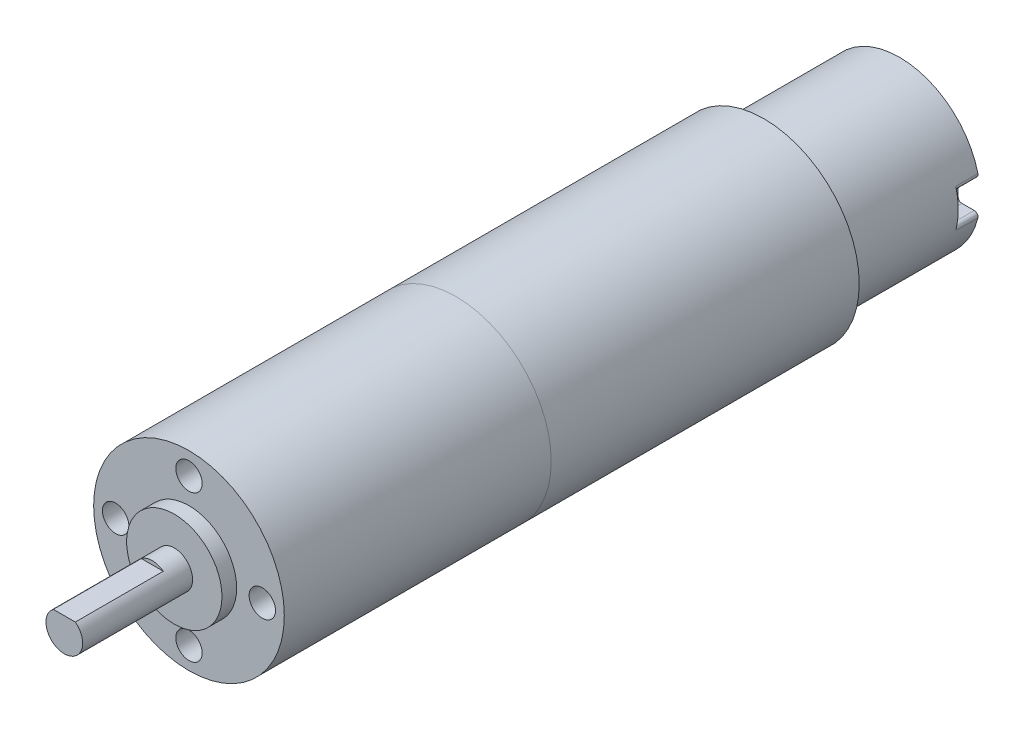
SolidWorks part; units mm, degrees
ref_plane "Plan de face" through (0, 0, 0) normal (0, 0, 1) x (1, 0, 0)
ref_plane "Plan de dessus" through (0, 0, 0) normal (0, 1, 0) x (1, 0, 0)
ref_plane "Plan de droite" through (0, 0, 0) normal (1, 0, 0) x (0, 0, -1)
sketch "Esquisse1" plane through (0, 0, 0) normal (0, 0, 1) x (1, 0, 0)
  circle A0 centre (0, 0) radius 13
  dimension "D1" = 26
extrude "Boss.-Extru. Reducteur" add sketch "Esquisse1" along normal blind 36.4
sketch "Esquisse2" plane through (0, 0, 36.4) normal (0, 0, 1) x (1, 0, 0)
  circle A0 centre (0, 0) radius 2.5
  dimension "D1" = 5
extrude "Boss.-Extru. Arbre" add sketch "Esquisse2" along normal blind 17
sketch "Esquisse4" plane through (0, 0, 36.4) normal (0, 0, 1) x (1, 0, 0)
  circle A0 centre (0, 0) radius 6.5
  circle A1 centre (0, 0) radius 2.5
extrude "Boss.-Extru.3" add sketch "Esquisse4" along normal blind 2
sketch "Esquisse5" plane through (0, 0, 36.4) normal (0, 0, 1) x (1, 0, 0)
  line L0 (0, 0) -> (10, 0) construction
  line L1 (0, 0) -> (0, 10) construction
  line L2 (0, 0) -> (-10, 0) construction
  line L3 (0, 0) -> (0, -10) construction
  circle A0 centre (0, 10) radius 1.8
  circle A1 centre (-10, 0) radius 1.8
  circle A2 centre (0, -10) radius 1.8
  circle A3 centre (10, 0) radius 1.8
extrude "Enlèv. mat.-Extru.2" cut sketch "Esquisse5" against normal blind 4
sketch "Esquisse6" plane through (0, 0, 53.4) normal (0, 0, 1) x (1, 0, 0)
  line L0 (0, -2.5) -> (0, 2) construction
  line L1 (0, 2) -> (1.5, 2)
  line L2 (0, 2) -> (-1.5, 2)
  circle A2 centre (0, 0) radius 2.5 construction
  circle A3 centre (0, 0) radius 2.5 construction
  arc A4 (-1.5, 2) -> (1.5, 2) centre (0, 0) cw
extrude "Enlèv. mat.-Extru.3" cut sketch "Esquisse6" against normal blind 12
sketch "Esquisse7" plane through (0, 0, 36.4) normal (0, 0, 1) x (1, 0, 0)
  circle A0 centre (0, 0) radius 2.4968
extrude "Boss.-Extru.4" add sketch "Esquisse7" along normal blind 3 separate body
sketch "Référence pour Assemblage" plane through (0, 0, 39.4) normal (0, 0, 1) x (1, 0, 0)
  circle A0 centre (0, 0) radius 2.5
sketch "Esquisse9" plane through (0, 0, 0) normal (0, 0, -1) x (-1, 0, 0)
  circle A0 centre (0, 0) radius 13
  dimension "D1" = 26
extrude "Boss.-Extru.5" add sketch "Esquisse9" along normal blind 42 separate body
sketch "Esquisse10" plane through (0, 0, -42) normal (0, 0, -1) x (-1, 0, 0)
  circle A0 centre (0, 0) radius 11
extrude "Boss.-Extru.6" add sketch "Esquisse10" along normal blind 18.5
sketch "Esquisse12" plane through (0, 0, -60.5) normal (0, 0, -1) x (-1, 0, 0)
  line L0 (0, 0) -> (0, -8) construction
  line L1 (0, -8) -> (7.5498, -8)
  line L2 (0, -8) -> (-7.5498, -8)
  line L3 (-11, 0) -> (-8, 0) construction
  line L4 (-8, 0) -> (-8, 2)
  line L5 (-8, 2) -> (-10.8167, 2)
  line L6 (-8, 0) -> (-8, -2)
  line L7 (-8, -2) -> (-10.8167, -2)
  circle A0 centre (0, 0) radius 11 construction
  arc A1 (-7.5498, -8) -> (7.5498, -8) centre (0, 0) ccw
  circle A2 centre (0, 0) radius 11 construction
  arc A3 (-10.8167, -2) -> (-10.8167, 2) centre (0, 0) cw
  circle M4 centre (0, 0) radius 11
  dimension "D1" = 8
  dimension "D2" = 3
  dimension "D3" = 2
  dimension "D4" = 2
extrude "Enlèv. mat.-Extru.5" cut sketch "Esquisse12" against normal blind 4 contours L1 L2 M4 region at (0, -9.2152, -60.5)
extrude "Enlèv. mat.-Extru.6" cut sketch "Esquisse12<4>" against normal blind 3 contours L7 L6 L4 L5 M4 region at (9.4701, 0, -60.5)
sketch "Esquisse12<4>" plane through (0, 0, -60.5) normal (0, 0, -1) x (-1, 0, 0) same geometry as "Esquisse12"
mirror "Symétrie1" about plane through (0, 0, 0) normal (1, 0, 0) of "Enlèv. mat.-Extru.6"
fillet "Congé1" radius 0.5 10 edges at (7.5498, -8, -58.5) (-7.5498, -8, -58.5) (-10.8167, 2, -59) (-10.8167, -2, -59) (-8, 2, -59) (-8, -2, -59) (8, -2, -59) (8, 2, -59) (10.8167, -2, -59) (10.8167, 2, -59)
